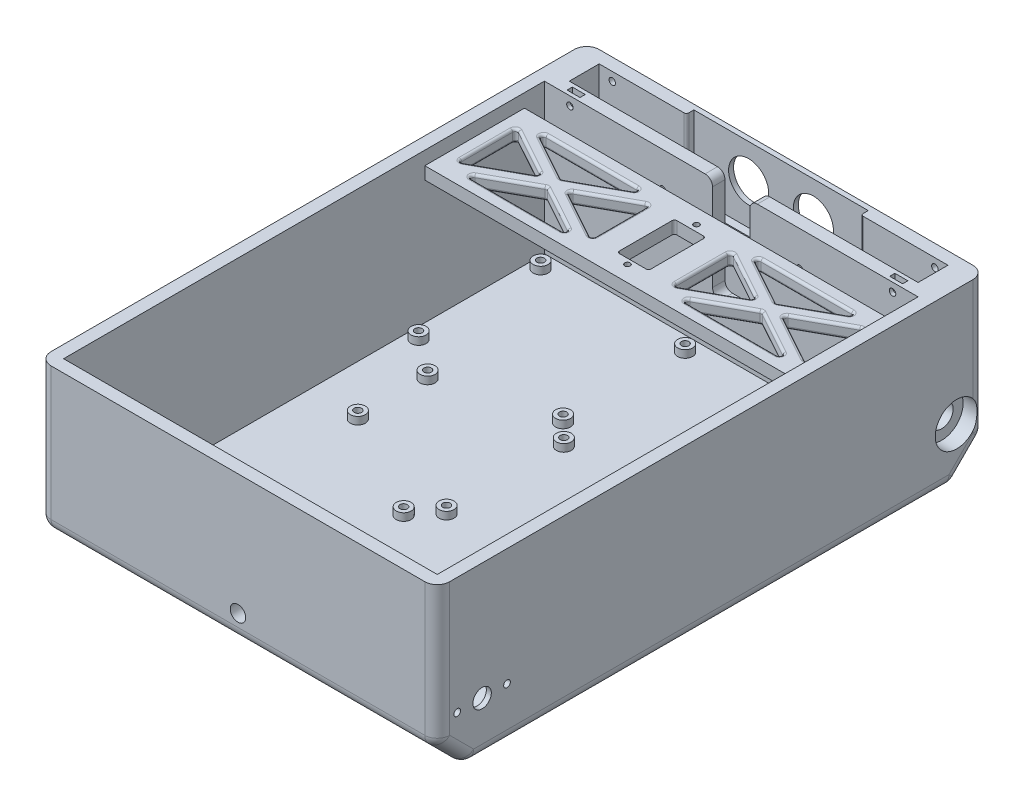
SolidWorks part; units mm, degrees
ref_plane "Front Plane" through (0, 0, 0) normal (0, 0, 1) x (1, 0, 0)
ref_plane "Top Plane" through (0, 0, 0) normal (0, 1, 0) x (1, 0, 0)
ref_plane "Right Plane" through (0, 0, 0) normal (1, 0, 0) x (0, 0, -1)
sketch "Main Body" plane through (0, 0, 0) normal (0, 1, 0) x (1, 0, 0)
  line L0 (-75, 110) -> (75, 110)
  line L1 (-75, -105) -> (75, -105)
  line L2 (-75, -105) -> (-75, 105)
  line L3 (-75, 105) -> (75, 105)
  line L4 (75, -105) -> (75, 105)
  line L5 (-75, -105) -> (75, 105) construction
  line L6 (-75, 105) -> (75, -105) construction
  line L7 (80, -105) -> (80, 105)
  line L8 (-75, -110) -> (75, -110)
  line L9 (-80, -105) -> (-80, 105)
  line L10 (-80, -110) -> (80, -110) construction
  line L11 (-80, -110) -> (-80, 110) construction
  line L12 (80, -110) -> (80, 110) construction
  line L13 (-80, 110) -> (80, 110) construction
  arc A0 (-75, -110) -> (-80, -105) centre (-75, -105) cw
  arc A1 (80, -105) -> (75, -110) centre (75, -105) cw
  arc A2 (75, 110) -> (80, 105) centre (75, 105) cw
  arc A3 (-75, 110) -> (-80, 105) centre (-75, 105) ccw
  point P0 (0, 0)
  dimension "D4" = 5
  dimension "D1" = 75
  dimension "D2" = 210
  dimension "D3" = 5
extrude "Boss-Extrude1" add sketch "Main Body" along normal blind 8 contours L1 L4 L3 L2 | L9 L8 L7 L0 L4 L1 L2 L3 region at (0, 0, -107.2797) region at (0, 0, 0)
extrude "Boss-Extrude3" add sketch "Main Body<4>" along normal blind 60 from surface starting at face at (0, 8, 0)
sketch "Main Body<4>" plane through (0, 0, 0) normal (0, 1, 0) x (1, 0, 0) same geometry as "Main Body"
sketch "Sketch1" plane through (75, 0, 0) normal (-1, 0, 0) x (0, 0, 1)
  line L0 (105, 68) -> (105, 8) construction
  line L1 (-105, 8) -> (105, 8) construction
  line L2 (79, 15.5) -> (105, 15.5)
  line L3 (79, 8) -> (105, 8)
  line L4 (79, 8) -> (79, 34)
  line L5 (79, 34) -> (105, 34)
  line L6 (105, 8) -> (105, 34)
  line L7 (79, 8) -> (105, 34) construction
  line L8 (79, 34) -> (105, 8) construction
  circle A0 centre (92, 21) radius 13
  line M2 (-105, 8) -> (105, 8)
  line M3 (105, 8) -> (105, 68)
  dimension "D1" = 26
  dimension "D2" = 7.5
extrude "Boss-Extrude4" add sketch "Sketch1" along normal up to surface (150 mm away) contours A0 L4 M2 | A0 L3 M3 region at (75, 10.5201, 82.0674) region at (75, 10.5201, 101.9326) up to face at (-75, 38, 0)
sketch "Sketch2" plane through (0, 0, 0) normal (1, 0, 0) x (0, 0, -1)
  line L0 (-105, 68) -> (-105, 15.5) construction
  line L1 (-105, 8) -> (-79, 8)
  line L2 (-105, 8) -> (-105, 15.5)
  line L3 (-105, 15.5) -> (-79, 15.5)
  line L4 (-79, 8) -> (-79, 15.5)
  line L5 (105, 8) -> (-79, 8) construction
  line L6 (-79, 8) -> (-79, 15.5) construction
  line L7 (-79, 15.5) -> (-80.2208, 15.5) construction
extrude "Cut-Extrude1" cut sketch "Sketch2" against normal mid plane 12
sketch "Sketch3" plane through (0, 8, 0) normal (0, 1, 0) x (1, 0, 0)
  line L0 (75, -105) -> (-75, -105) construction
  line L1 (-4, -79) -> (-11, -79)
  line L2 (-4, -79) -> (-4, -105)
  line L3 (-4, -105) -> (-11, -105)
  line L4 (-11, -79) -> (-11, -105)
  line L5 (0, 0) -> (0, -105) construction
  line L6 (-75, -79) -> (-6, -79) construction
  line L7 (11, -79) -> (11, -105)
  line L8 (4, -105) -> (11, -105)
  line L9 (4, -79) -> (4, -105)
  line L10 (4, -79) -> (11, -79)
  line L11 (-6, -103.7792) -> (-6, -92) construction
  dimension "D1" = 5
  dimension "D2" = 4
extrude "Boss-Extrude5" add sketch "Sketch3" along normal blind 20
sketch "Sketch4" plane through (0, 8, 0) normal (0, 1, 0) x (1, 0, 0)
  line L0 (-75, -105) -> (-75, 105) construction
  line L1 (-75, 93) -> (75, 93)
  line L2 (-75, 93) -> (-75, 88)
  line L3 (-75, 88) -> (75, 88)
  line L4 (75, 93) -> (75, 88)
  line L5 (75, 105) -> (75, -105) construction
  line L6 (-75, 105) -> (75, 105) construction
  dimension "D1" = 17
  dimension "D2" = 5
extrude "Boss-Extrude6" add sketch "Sketch4" along normal up to surface (60 mm away) up to face at (0, 68, 0)
sketch "Sketch5" plane through (80, 0, 0) normal (1, 0, 0) x (0, 0, -1)
  circle A0 centre (-92, 21) radius 3.5 construction
  circle A1 centre (-92, 21) radius 3.5
  circle A2 centre (-92, 21) radius 3.7
  dimension "D1" = 0.2
extrude "Cut-Extrude4" cut sketch "Sketch5" against normal up to next contours A1 | A2 A1 region at (80, 21, 92) region at (80, 21, 95.5953)
sketch "Sketch6" plane through (-75, 0, 0) normal (1, 0, 0) x (0, 0, -1)
  circle A0 centre (-92, 21) radius 13
  dimension "D1" = 26
extrude "Cut-Extrude5" cut sketch "Sketch6" against normal offset from surface (3 mm away) 2 up to face at (-80, 34, 0)
mirror "Mirror1" about plane through (0, 0, 0) normal (1, 0, 0) of "Cut-Extrude4"
sketch "Sketch8" plane through (75, 0, 0) normal (-1, 0, 0) x (0, 0, 1)
  circle A0 centre (92, 21) radius 13
  dimension "D1" = 26
extrude "Cut-Extrude6" cut sketch "Sketch8" against normal offset from surface (3 mm away) 2 up to face at (80, 21, 88.3)
sketch "Sketch10" plane through (80, 0, 0) normal (1, 0, 0) x (0, 0, -1)
  circle A1 centre (-82, 21) radius 1.25
  circle A2 centre (-82, 21) radius 1.25
  circle A3 centre (-102, 21) radius 1.25
  circle A4 centre (-102, 21) radius 1.25
  circle A5 centre (-92, 21) radius 12.5
  circle A6 centre (-92, 21) radius 12.5
  circle A63 centre (-102, 21) radius 1.35
  circle A64 centre (-82, 21) radius 1.35
  dimension "D1" = 0
  dimension "D2" = 0
  dimension "D3" = 0
  dimension "D4" = 0.1
  dimension "D5" = 0.1
extrude "Cut-Extrude7" cut sketch "Sketch10" against normal up to next contours A2 | A64 A2 | A4 | A63 A4 region at (80, 21, 82) region at (80, 21, 102) region at (80, 21, 103.3118) region at (80, 21, 83.3118)
mirror "Mirror3" about plane through (0, 0, 0) normal (1, 0, 0) of "Cut-Extrude7"
sketch "Sketch11" plane through (80, 0, 0) normal (1, 0, 0) x (0, 0, -1)
  circle A0 centre (98.5, 21) radius 4.5 construction
  circle A1 centre (98.5, 21) radius 4.5
  circle A3 centre (98.5, 21) radius 4.6
  dimension "D1" = 0.1
extrude "Cut-Extrude10" cut sketch "Sketch11" against normal through all contours A1 | A3 A1 region at (80, 21, -98.5) region at (80, 21, -93.913)
sketch "Sketch12" plane through (-75, 0, 0) normal (1, 0, 0) x (0, 0, -1)
  line L0 (93, 8) -> (105, 8) construction
  line L1 (93, 68) -> (105, 68)
  line L2 (93, 68) -> (93, 8)
  line L3 (93, 8) -> (105, 8)
  line L4 (105, 68) -> (105, 8)
  line L6 (93, 68) -> (93, 8) construction
  line L7 (93, 68) -> (105, 68) construction
  circle A2 centre (98.5, 21) radius 4.6 construction
  circle A3 centre (98.5, 21) radius 4.6
extrude "Boss-Extrude7" add sketch "Sketch12" along normal blind 5
sketch "Sketch13" plane through (-80, 0, 0) normal (-1, 0, 0) x (0, 0, 1)
  circle A0 centre (-98.5, 21) radius 8.6
  circle A2 centre (-98.5, 21) radius 4.6 construction
  dimension "D1" = 17.2
extrude "Cut-Extrude11" cut sketch "Sketch13" against normal blind 6
mirror "Mirror4" about plane through (0, 0, 0) normal (1, 0, 0) of "Boss-Extrude7", "Cut-Extrude11"
sketch "Sketch14" plane through (0, 8, 0) normal (0, 1, 0) x (1, 0, 0)
  line L0 (-4, -105) -> (-4, -79) construction
  line L1 (-4, -95) -> (4, -95)
  line L2 (-4, -95) -> (-4, -105)
  line L3 (-4, -105) -> (4, -105)
  line L4 (4, -95) -> (4, -105)
  dimension "D1" = 10
extrude "Boss-Extrude9" add sketch "Sketch14" along normal blind 5
sketch "Sketch15" plane through (0, 0, 110) normal (0, 0, 1) x (1, 0, 0)
  arc A0 (-3, 19.5) -> (3, 19.5) centre (0, 19.5) ccw construction
  arc A1 (-3, 19.5) -> (3, 19.5) centre (0, 19.5) ccw
  arc A2 (3, 19.5) -> (-3, 19.5) centre (0, 19.5) ccw construction
  arc A3 (3, 19.5) -> (-3, 19.5) centre (0, 19.5) ccw
  arc A4 (3.1, 19.5) -> (-3.1, 19.5) centre (0, 19.5) ccw
  arc A5 (-3.1, 19.5) -> (3.1, 19.5) centre (0, 19.5) ccw
  dimension "D1" = 0.1
extrude "Cut-Extrude12" cut sketch "Sketch15" against normal up to next contours A1 A3 | A4 A5 A3 A1 region at (0, 19.5, 110) region at (0, 16.4877, 110)
sketch "Sketch16" plane through (0, 0, 0) normal (0, -1, 0) x (1, 0, 0)
  circle A0 centre (-12.5, -82) radius 1.475 construction
  circle A1 centre (-70.5, -82) radius 1.475 construction
  circle A2 centre (-70.5, -33) radius 1.475 construction
  circle A3 centre (-12.5, -33) radius 1.475 construction
  circle A4 centre (-4.2, -25) radius 1.475 construction
  circle A5 centre (-55, -21.12) radius 1.475 construction
  circle A6 centre (-55, 6.88) radius 1.475 construction
  circle A7 centre (-4.2, 22.08) radius 1.475 construction
  circle A8 centre (-12.3, 31.18) radius 1.475 construction
  circle A9 centre (24.2, 31.18) radius 1.475 construction
  circle A10 centre (37.8459, 24.117) radius 1.475 construction
  circle A11 centre (59.5541, 24.117) radius 1.475 construction
  circle A12 centre (59.5541, 68.243) radius 1.475 construction
  circle A13 centre (37.8459, 68.243) radius 1.475 construction
  circle A14 centre (24.2, 67.68) radius 1.475 construction
  circle A15 centre (-12.3, 67.68) radius 1.475 construction
  circle A16 centre (-12.5, -82) radius 1.475
  circle A17 centre (-70.5, -82) radius 1.475
  circle A18 centre (-70.5, -33) radius 1.475
  circle A19 centre (-12.5, -33) radius 1.475
  circle A20 centre (-4.2, -25) radius 1.475
  circle A21 centre (-55, -21.12) radius 1.475
  circle A22 centre (-55, 6.88) radius 1.475
  circle A23 centre (-4.2, 22.08) radius 1.475
  circle A24 centre (-12.3, 31.18) radius 1.475
  circle A25 centre (24.2, 31.18) radius 1.475
  circle A26 centre (37.8459, 24.117) radius 1.475
  circle A27 centre (59.5541, 24.117) radius 1.475
  circle A28 centre (59.5541, 68.243) radius 1.475
  circle A29 centre (37.8459, 68.243) radius 1.475
  circle A30 centre (24.2, 67.68) radius 1.475
  circle A31 centre (-12.3, 67.68) radius 1.475
extrude "Cut-Extrude13" cut sketch "Sketch16" against normal up to next
sketch "Sketch17" plane through (0, 8, 0) normal (0, 1, 0) x (1, 0, 0)
  line L0 (0, 88) -> (0, -110) construction
  line L1 (-75, 88) -> (75, 88) construction
  line L2 (75, -110) -> (-75, -110) construction
  line L3 (-75, 4.5) -> (75, 4.5) construction
  line L7 (-75, -79) -> (-75, 88) construction
  line L8 (75, 88) -> (75, -79) construction
  circle A0 centre (-70.5, 82) radius 3
  circle A1 centre (-12.5, 82) radius 3
  circle A2 centre (-12.3, -67.68) radius 1.475
  circle A3 centre (-12.3, -67.68) radius 1.475
  circle A4 centre (24.2, -67.68) radius 1.475
  circle A5 centre (24.2, -67.68) radius 1.475
  circle A6 centre (37.8459, -68.243) radius 1.475
  circle A7 centre (37.8459, -68.243) radius 1.475
  circle A8 centre (59.5541, -68.243) radius 1.475
  circle A9 centre (59.5541, -68.243) radius 1.475
  circle A10 centre (59.5541, -24.117) radius 1.475
  circle A11 centre (59.5541, -24.117) radius 1.475
  circle A12 centre (37.8459, -24.117) radius 1.475
  circle A13 centre (37.8459, -24.117) radius 1.475
  circle A14 centre (24.2, -31.18) radius 1.475
  circle A15 centre (24.2, -31.18) radius 1.475
  circle A16 centre (-12.3, -31.18) radius 1.475
  circle A17 centre (-12.3, -31.18) radius 1.475
  circle A18 centre (-4.2, -22.08) radius 1.475
  circle A19 centre (-4.2, -22.08) radius 1.475
  circle A20 centre (-55, -6.88) radius 1.475
  circle A21 centre (-55, -6.88) radius 1.475
  circle A22 centre (-55, 21.12) radius 1.475
  circle A23 centre (-55, 21.12) radius 1.475
  circle A24 centre (-4.2, 25) radius 1.475
  circle A25 centre (-4.2, 25) radius 1.475
  circle A26 centre (-12.5, 33) radius 1.475
  circle A27 centre (-12.5, 33) radius 1.475
  circle A28 centre (-70.5, 33) radius 1.475
  circle A29 centre (-70.5, 33) radius 1.475
  circle A30 centre (-70.5, 82) radius 1.475
  circle A31 centre (-70.5, 82) radius 1.475
  circle A32 centre (-12.5, 82) radius 1.475
  circle A33 centre (-12.5, 82) radius 1.475
  circle A34 centre (-70.5, 33) radius 3
  circle A35 centre (-55, 21.12) radius 3
  circle A36 centre (-12.5, 33) radius 3
  circle A37 centre (-4.2, 25) radius 3
  circle A38 centre (-55, -6.88) radius 3
  circle A39 centre (-4.2, -22.08) radius 3
  circle A40 centre (-12.3, -31.18) radius 3
  circle A41 centre (24.2, -31.18) radius 3
  circle A42 centre (37.8459, -24.117) radius 3
  circle A43 centre (59.5541, -24.117) radius 3
  circle A44 centre (-12.3, -67.68) radius 3
  circle A45 centre (24.2, -67.68) radius 3
  circle A46 centre (37.8459, -68.243) radius 3
  circle A47 centre (59.5541, -68.243) radius 3
  dimension "D1" = 6
  dimension "D2" = 0
  dimension "D3" = 0
  dimension "D4" = 0
  dimension "D5" = 0
  dimension "D6" = 0
  dimension "D7" = 0
  dimension "D8" = 0
  dimension "D9" = 0
  dimension "D10" = 0
  dimension "D11" = 0
  dimension "D12" = 0
  dimension "D13" = 0
  dimension "D14" = 0
  dimension "D15" = 0
  dimension "D16" = 0
  dimension "D17" = 0
extrude "Boss-Extrude10" add sketch "Sketch17" along normal blind 3
sketch "Sketch18" plane through (75, 0, 0) normal (-1, 0, 0) x (0, 0, 1)
  line L1 (-80, 62.6) -> (-40, 62.6)
  line L2 (-80, 62.6) -> (-80, 57.6)
  line L3 (-80, 57.6) -> (-40, 57.6)
  line L4 (-40, 62.6) -> (-40, 57.6)
  line L5 (-88, 68) -> (105, 68) construction
  dimension "D1" = 5
  dimension "D2" = 30
  dimension "D3" = 40
  dimension "D4" = 5.4
extrude "Boss-Extrude11" add sketch "Sketch18" along normal up to next
sketch "Sketch19" plane through (0, 68, 0) normal (0, 1, 0) x (1, 0, 0)
  line L1 (-6.3, 71.5) -> (6.3, 71.5)
  line L2 (-6.3, 71.5) -> (-6.3, 48.5)
  line L3 (-6.3, 48.5) -> (6.3, 48.5)
  line L4 (6.3, 71.5) -> (6.3, 48.5)
  line L12 (-75, 80) -> (-75, 40)
  line L13 (-75, 40) -> (75, 40)
  line L14 (75, 40) -> (75, 80)
  line L15 (75, 80) -> (-75, 80)
  line L16 (-75, 80) -> (-75, 40)
  line L17 (-75, 40) -> (75, 40)
  line L18 (75, 40) -> (75, 80)
  line L19 (75, 80) -> (-75, 80)
  point P4 (0, 71.5)
  point P8 (0, 80)
  point P12 (6.3, 60)
  point P13 (75, 60)
  dimension "D1" = 23
  dimension "D2" = 12.6
  dimension "D3" = 0
extrude "Cut-Extrude14" cut sketch "Sketch19" against normal up to next contours L4 L1 L2 L3 region at (0, 68, -60)
sketch "Sketch21" plane through (0, 0, -110) normal (0, 0, -1) x (-1, 0, 0)
  circle A1 centre (-64.75, 64.5) radius 1.3
  circle A2 centre (-64.75, 64.5) radius 1.3
  circle A3 centre (64.75, 64.5) radius 1.3
  circle A4 centre (64.75, 64.5) radius 1.3
  dimension "D1" = 0
  dimension "D2" = 0
extrude "Cut-Extrude16" cut sketch "Sketch21" against normal up to surface (22 mm away) up to face at (0, 38, -88)
ref_plane "Plane1" through (0, 0, -90.5) normal (0, 0, -1) x (-1, 0, 0)
sketch "Sketch22" plane through (0, 0, -90.5) normal (0, 0, -1) x (-1, 0, 0)
  line L0 (-67.35, 66.0011) -> (-67.35, 68)
  line L1 (-62.15, 66.0011) -> (-64.75, 67.5022)
  line L2 (-64.75, 67.5022) -> (-67.35, 66.0011)
  line L3 (-67.35, 66.0011) -> (-67.35, 62.9989)
  line L4 (-67.35, 62.9989) -> (-64.75, 61.4978)
  line L5 (-64.75, 61.4978) -> (-62.15, 62.9989)
  line L6 (-62.15, 62.9989) -> (-62.15, 66.0011)
  line L7 (-67.35, 68) -> (-62.15, 68)
  line L8 (-62.15, 68) -> (-62.15, 66.0011)
  line L9 (70, 68) -> (-70, 68) construction
  line L10 (0, 0) -> (0, 68) construction
  line L11 (75, 68) -> (-75, 68) construction
  line L12 (64.75, 61.4978) -> (62.15, 62.9989)
  line L13 (67.35, 62.9989) -> (64.75, 61.4978)
  line L14 (64.75, 67.5022) -> (67.35, 66.0011)
  line L15 (67.35, 66.0011) -> (67.35, 62.9989)
  line L16 (67.35, 66.0011) -> (67.35, 68)
  line L17 (62.15, 62.9989) -> (62.15, 66.0011)
  line L18 (62.15, 68) -> (62.15, 66.0011)
  line L19 (67.35, 68) -> (62.15, 68)
  line L20 (62.15, 66.0011) -> (64.75, 67.5022)
  circle A0 centre (-64.75, 64.5) radius 2.6 construction
  dimension "D1" = 5.2
extrude "Cut-Extrude17" cut sketch "Sketch22" against normal mid plane 2.1 contours L20 L17 L12 L13 L15 L14 | L18 L20 L14 L16 L19 | L5 L6 L1 L2 L3 L4 | L8 L7 L0 L2 L1 region at (67.2943, 67.0006, -90.5) region at (64.75, 64.5, -90.5) region at (-64.75, 64.5, -90.5) region at (-62.2057, 67.0006, -90.5)
sketch "Sketch23" plane through (0, 0, -110) normal (0, 0, -1) x (-1, 0, 0)
  circle A0 centre (64.75, 64.5) radius 2.5
  circle A1 centre (-64.75, 64.5) radius 2.5
  dimension "D1" = 5
  dimension "D2" = 5
extrude "Cut-Extrude18" cut sketch "Sketch23" against normal mid plane 2.5
sketch "Sketch24" plane through (0, 62.6, 0) normal (0, 1, 0) x (1, 0, 0)
  circle A0 centre (0, 46.35) radius 1.1002
  arc A1 (0.4, 45.4333) -> (-0.4, 45.4333) centre (0, 46.35) ccw construction
  circle A2 centre (0, 74.05) radius 1.1002
  arc A3 (-0.4, 74.9667) -> (0, 73.0498) centre (0, 74.05) ccw construction
  point P5 (0.4, 45.4333)
  dimension "D1" = 0.1
extrude "Cut-Extrude19" cut sketch "Sketch24" against normal up to next
sketch "Sketch25" plane through (0, 62.6, 0) normal (0, 1, 0) x (1, 0, 0)
  line L0 (6.3, 71.5) -> (6.3, 48.5) construction
  line L1 (-11.3, 80) -> (11.3, 80)
  line L2 (-11.3, 80) -> (-11.3, 40)
  line L3 (-11.3, 40) -> (11.3, 40)
  line L4 (-75, 80) -> (-75, 40)
  line L5 (-75, 40) -> (75, 40)
  line L6 (75, 40) -> (75, 80)
  line L7 (75, 80) -> (-75, 80)
  line L8 (-75, 80) -> (-75, 40)
  line L9 (-75, 40) -> (75, 40)
  line L10 (75, 40) -> (75, 80)
  line L11 (75, 80) -> (-75, 80)
  line L12 (11.3, 80) -> (11.3, 40)
  line L13 (-11.3, 80) -> (11.3, 40) construction
  line L14 (-11.3, 40) -> (11.3, 80) construction
  line L15 (0, 80) -> (0, 40) construction
  line L16 (70, 75) -> (70, 45)
  line L17 (-70, 75) -> (-16.3, 75)
  line L18 (-70, 75) -> (-70, 45)
  line L19 (-70, 45) -> (-16.3, 45)
  line L20 (-16.3, 75) -> (-16.3, 45)
  line L21 (-70, 75) -> (-16.3, 45) construction
  line L22 (-70, 45) -> (-16.3, 75) construction
  line L23 (70, 75) -> (16.3, 45) construction
  line L24 (70, 45) -> (16.3, 75) construction
  line L25 (70, 75) -> (16.3, 75)
  line L26 (16.3, 75) -> (16.3, 45)
  line L27 (70, 45) -> (16.3, 45)
  line L28 (-75, 60) -> (-11.3, 60) construction
  line L29 (75, 60) -> (11.3, 60) construction
  line L30 (-70, 71.9362) -> (-48.3314, 60)
  line L31 (-16.3, 71.9362) -> (-37.9686, 60)
  line L32 (70, 71.9362) -> (48.3314, 60)
  line L33 (-48.3314, 60) -> (-70, 48.0638)
  line L34 (48.3314, 60) -> (70, 48.0638)
  line L35 (-65.199, 45) -> (-43.15, 57.1458)
  line L36 (65.199, 45) -> (43.15, 57.1458)
  line L37 (-43.15, 57.1458) -> (-21.101, 45)
  line L38 (43.15, 57.1458) -> (21.101, 45)
  line L39 (16.3, 71.9362) -> (37.9686, 60)
  line L40 (-37.9686, 60) -> (-16.3, 48.0638)
  line L41 (37.9686, 60) -> (16.3, 48.0638)
  line L42 (-65.199, 75) -> (-43.15, 62.8542)
  line L43 (65.199, 75) -> (43.15, 62.8542)
  line L44 (-43.15, 62.8542) -> (-21.101, 75)
  line L45 (43.15, 62.8542) -> (21.101, 75)
  line L46 (-75, 40) -> (-75, 80) construction
  line L47 (-75, 40) -> (75, 40) construction
  point P2 (0, 60)
  point P9 (-43.15, 60)
  point P10 (75, 60)
  point P24 (43.15, 60)
  point P62 (-54.1745, 68.9271)
  dimension "D2" = 5
  dimension "D3" = 5
  dimension "D4" = 5
  dimension "D5" = 5
  dimension "D6" = 26.6686
  dimension "D1" = 0
extrude "Cut-Extrude21" cut sketch "Sketch25" against normal up to next contours L37 L35 L19 | L33 L30 L18 | L42 L44 L17 | L31 L40 L20 | L41 L39 L26 | L45 L43 L25 | L36 L38 L27 | L32 L34 L16 region at (62.7771, 62.6, -60) region at (43.15, 62.6, -70.9514) region at (43.15, 62.6, -49.0486) region at (23.5229, 62.6, -60) region at (-43.15, 62.6, -70.9514) region at (-62.7771, 62.6, -60) region at (-23.5229, 62.6, -60) region at (-43.15, 62.6, -49.0486)
sketch "Sketch26" plane through (-80, 0, 0) normal (-1, 0, 0) x (0, 0, 1)
  line L0 (-110, 12.5093) -> (-97.4907, 0)
  line L1 (-110, 68) -> (-110, 0) construction
  line L2 (105, 0) -> (-105, 0) construction
  line L3 (-97.4907, 0) -> (-92.4907, 0)
  line L4 (-92.4907, 0) -> (-110, 17.5093)
  line L5 (-110, 17.5093) -> (-110, 12.5093)
  line L6 (-110, 12.5093) -> (-110, 0)
  line L7 (-110, 0) -> (-97.4907, 0)
  circle A1 centre (-98.5, 21) radius 8.6 construction
  line M5 (-105, 15.3688) -> (-105, 0)
  line M6 (-105, 0) -> (105, 0)
  dimension "D1" = 2
  dimension "D2" = 5
  dimension "D3" = 45
extrude "Cut-Extrude22" cut sketch "Sketch26" against normal up to next contours L6 L7 L0 M5 | L0 M5 M6 region at (-80, 5.1087, -107.7081) region at (-80, 2.5031, -102.4969)
mirror "Mirror5" about plane through (0, 0, 0) normal (0, 0, 1) of "Cut-Extrude22"
fillet "Fillet1" radius 5 14 edges at (80, 3.7547, -101.2453) (78.5355, 11.0449, -108.5355) (-80, 3.7547, -101.2453) (-78.5355, 11.0449, -108.5355) (80, 3.7547, 101.2453) (78.5355, 11.0449, 108.5355) (-80, 3.7547, 101.2453) (-78.5355, 11.0449, 108.5355) (0, 0, -97.4907) (0, 12.5093, -110) (0, 0, 97.4907) (0, 12.5093, 110) (-80, 0, 0) (80, 0, 0)
fillet "Fillet2" radius 1 76 edges at (-32.1255, 57.6, -51.0729) (-32.1255, 62.6, -51.0729) (-21.101, 60.1, -45) (-43.15, 62.6, -45) (-43.15, 57.6, -45) (-54.1745, 57.6, -51.0729) (-65.199, 60.1, -45) (-54.1745, 62.6, -51.0729) (-43.15, 60.1, -57.1458) (32.1255, 57.6, -68.9271) (32.1255, 62.6, -68.9271) (21.101, 60.1, -75) (43.15, 62.6, -75) (43.15, 57.6, -75) (54.1745, 57.6, -68.9271) (65.199, 60.1, -75) (54.1745, 62.6, -68.9271) (43.15, 60.1, -62.8542) (54.1745, 62.6, -51.0729) (54.1745, 57.6, -51.0729) (43.15, 57.6, -45) (65.199, 60.1, -45) (43.15, 62.6, -45) (21.101, 60.1, -45) (32.1255, 62.6, -51.0729) (43.15, 60.1, -57.1458) (32.1255, 57.6, -51.0729) (59.1657, 62.6, -65.9681) (59.1657, 57.6, -65.9681) (70, 57.6, -60) (70, 60.1, -71.9362) (70, 62.6, -60) (70, 60.1, -48.0638) (59.1657, 62.6, -54.0319) (48.3314, 60.1, -60) (59.1657, 57.6, -54.0319) (-54.1745, 62.6, -68.9271) (-54.1745, 57.6, -68.9271) (-43.15, 57.6, -75) (-65.199, 60.1, -75) (-43.15, 62.6, -75) (-21.101, 60.1, -75) (-32.1255, 62.6, -68.9271) (-43.15, 60.1, -62.8542) (-32.1255, 57.6, -68.9271) (-59.1657, 57.6, -54.0319) (-59.1657, 62.6, -54.0319) (-70, 60.1, -48.0638) (-70, 62.6, -60) (-70, 57.6, -60) (-59.1657, 57.6, -65.9681) (-70, 60.1, -71.9362) (-59.1657, 62.6, -65.9681) (-48.3314, 60.1, -60) (-27.1343, 62.6, -65.9681) (-27.1343, 57.6, -65.9681) (-16.3, 57.6, -60) (-16.3, 60.1, -71.9362) (-16.3, 62.6, -60) (-16.3, 60.1, -48.0638) (-27.1343, 62.6, -54.0319) (-37.9686, 60.1, -60) (-27.1343, 57.6, -54.0319) (27.1343, 57.6, -54.0319) (27.1343, 62.6, -54.0319) (16.3, 60.1, -48.0638) (16.3, 62.6, -60) (16.3, 57.6, -60) (27.1343, 57.6, -65.9681) (16.3, 60.1, -71.9362) (27.1343, 62.6, -65.9681) (37.9686, 60.1, -60) (6.3, 60.1, -48.5) (-6.3, 60.1, -48.5) (-6.3, 60.1, -71.5) (6.3, 60.1, -71.5)
sketch "Sketch33" plane through (0, 0, -110) normal (0, 0, -1) x (-1, 0, 0)
  circle A0 centre (-13, 53.9999) radius 8.05
  circle A1 centre (13, 53.9999) radius 8.05
  circle A2 centre (-13, 53.9999) radius 7.3 construction
  circle A3 centre (13, 53.9999) radius 7.3 construction
  dimension "D1" = 16.1
extrude "Cut-Extrude27" cut sketch "Sketch33" against normal up to next
sketch "Sketch34" plane through (0, 0, -93) normal (0, 0, -1) x (-1, 0, 0)
  circle A0 centre (27.525, 54) radius 1.3 construction
  circle A1 centre (27.525, 54) radius 1.3
  circle A2 centre (-27.525, 54) radius 1.3 construction
  circle A3 centre (-27.525, 54) radius 1.3
extrude "Cut-Extrude28" cut sketch "Sketch34" against normal up to next
sketch "Sketch35" plane through (0, 68, 0) normal (0, 1, 0) x (1, 0, 0)
  line L0 (70, 93) -> (-70, 93) construction
  line L1 (-7.5, 93) -> (7.5, 93)
  line L2 (-7.5, 93) -> (-7.5, 88)
  line L3 (-7.5, 88) -> (7.5, 88)
  line L4 (7.5, 93) -> (7.5, 88)
  line L5 (-7.5, 93) -> (7.5, 88) construction
  line L6 (-7.5, 88) -> (7.5, 93) construction
  line L7 (-75, 88) -> (75, 88) construction
  point P0 (0, 90.5)
  point P5 (0, 0)
  point P9 (15.3298, 88)
  dimension "D1" = 15
extrude "Cut-Extrude29" cut sketch "Sketch35" against normal offset from surface (41 mm away) 19 up to face at (37.8459, 8, 71.243)
fillet "Fillet4" radius 3 9 edges at (0, 8, 95) (-7.5, 28, 79) (-7.5, 28, 105) (7.5, 28, 105) (7.5, 28, 79) (-7.5, 68, -90.5) (7.5, 68, -90.5) (-7.5, 27, -90.5) (7.5, 27, -90.5)
fillet "Fillet5" radius 1 1 edges at (0, 13, 95)
sketch "Sketch36" plane through (0, 68, 0) normal (0, 1, 0) x (1, 0, 0)
  line L0 (-70, 105) -> (70, 105) construction
  line L1 (-35, 108) -> (35, 108)
  line L2 (-35, 108) -> (-35, 105)
  line L3 (-35, 105) -> (35, 105)
  line L4 (35, 108) -> (35, 105)
  line L5 (-75, 110) -> (75, 110) construction
  point P6 (0, 108)
  dimension "D1" = 70
  dimension "D2" = 2
extrude "Cut-Extrude30" cut sketch "Sketch36" against normal blind 30
fillet "Fillet6" radius 1 2 edges at (35, 53, -105) (-35, 53, -105)
